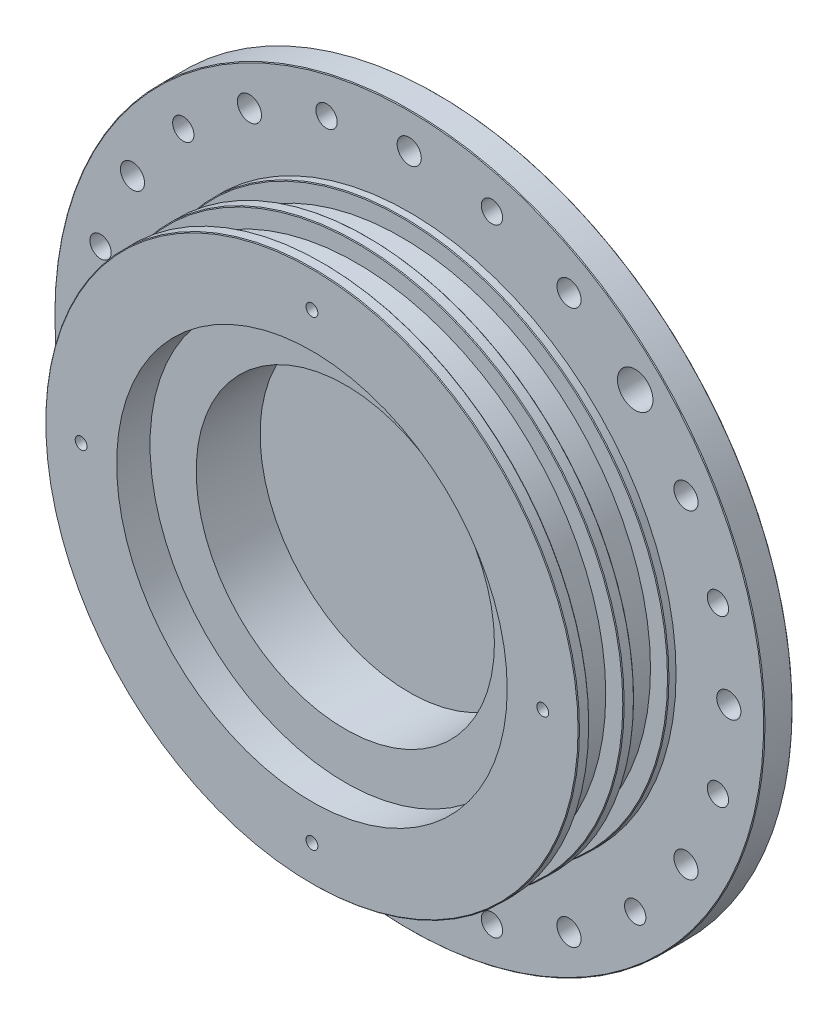
SolidWorks part; units mm, degrees
other "Marquage1"
sketch "Esquisse22" plane through (-100, 100, -114.225) normal (-0.6969, 0.6451, 0.3132) x (0.5706, 0.7634, -0.3027)
sketch "Esquisse26" plane through (-110, 110, -114.225) normal (-0.6969, 0.6451, 0.3132) x (0.5706, 0.7634, -0.3027)
sketch "Esquisse28" plane through (-110, 110, -114.225) normal (-0.6969, 0.6451, 0.3132) x (0.5706, 0.7634, -0.3027)
sketch "Esquisse31" plane through (-110, 110, -114.225) normal (-0.6969, 0.6451, 0.3132) x (0.5706, 0.7634, -0.3027)
sketch "Esquisse32" plane through (-100, 100, -114.225) normal (-0.6969, 0.6451, 0.3132) x (0.5706, 0.7634, -0.3027)
material "AISI 316 Barre d'acier inoxydable recuit (SS)"
ref_plane "Plan de face" through (0, 0, 0) normal (0, 0, 1) x (1, 0, 0)
ref_plane "Plan de dessus" through (0, 0, 0) normal (0, 1, 0) x (1, 0, 0)
ref_plane "Plan de droite" through (0, 0, 0) normal (1, 0, 0) x (0, 0, -1)
sketch "Esquisse1" plane through (0, 0, 0) normal (0, 1, 0) x (1, 0, 0)
  line L0 (87.5, 35.4) -> (0, 35.4)
  line L1 (0, 35.4) -> (0, 0)
  line L2 (0, 0) -> (75.15, 0)
  line L3 (75.15, 0) -> (75.15, 3)
  line L4 (75.15, 3) -> (70.15, 3)
  line L5 (70.15, 3) -> (70.15, 12.6)
  line L6 (70.15, 12.6) -> (75.15, 12.6)
  line L7 (75.15, 12.6) -> (75.15, 15.6)
  line L8 (75.15, 15.6) -> (70.15, 15.6)
  line L9 (70.15, 15.6) -> (70.15, 25.2)
  line L10 (70.15, 25.2) -> (75.15, 25.2)
  line L11 (75.15, 25.2) -> (75.15, 27.4)
  line L12 (75.15, 27.4) -> (87.5, 27.4)
  line L13 (87.5, 27.4) -> (87.5, 35.4)
  line L14 (0, 35.4) -> (0, 0) construction
  dimension "D1" = 8
  dimension "D2" = 2.2
  dimension "D3" = 9.6
  dimension "D4" = 3
  dimension "D5" = 9.6
  dimension "D6" = 3
  dimension "D7" = 5
  dimension "D8" = 75.15
  dimension "D9" = 87.5
revolve "Révolution1" add sketch "Esquisse1" angle 360 about L14 reverse direction yes
hole_wizard "Diamètre du perçage Ø9.0 (9)1" positions "Esquisse3" profile "Esquisse2" hole size "Ø9.0" standard "Ansi Metric"
sketch "Esquisse3" plane through (0, 0, -27.4) normal (0, 0, 1) x (1, 0, 0)
  point P0 (-87.5, 0)
  point P1 (0, 87.5)
  point P2 (0, -87.5)
  point P3 (87.5, 0)
sketch "Esquisse2" plane through (-87.5, 0, -27.4) normal (1, 0, 0) x (0, -1, 0)
  line L0 (0, 0) -> (0, 3)
  line L1 (0, 3) -> (4.5, 3)
  line L2 (4.5, 3) -> (4.5, 0)
  line L5 (4.5, 0) -> (0, 0)
  line L10 (0, 3) -> (-4.5, 3) construction
  line L11 (0, -6.35) -> (0, 107.95) construction
  dimension "Diamètre du perçage" = 9
  dimension "Profondeur du perçage" = 3
  dimension "Angle de pointe" = 180
hole_wizard "Dégagement M31" positions "Esquisse5" profile "Esquisse4" hole size "M3" standard "Ansi Metric"
sketch "Esquisse5" plane through (0, 0, 0) normal (0, 0, 1) x (1, 0, 0)
  point P0 (-65, 0)
  point P1 (65, 0)
  point P2 (0, 65)
  point P3 (0, -65)
sketch "Esquisse4" plane through (-65, 0, 0) normal (1, 0, 0) x (0, -1, 0)
  line L0 (0, 0) -> (0, 17.001)
  line L1 (0, 17.001) -> (1.666, 16)
  line L2 (1.666, 16) -> (1.666, 0)
  line L5 (1.666, 0) -> (0, 0)
  line L10 (0, 17.001) -> (-1.666, 16) construction
  line L11 (0, -6.35) -> (0, 107.95) construction
  dimension "Diamètre du perçage" = 3.332
  dimension "Profondeur du perçage" = 16
  dimension "Angle de pointe" = 118
hole_wizard "Dégagement M1001" positions "Esquisse7" profile "Esquisse6" hole size "M100" standard "Ansi Metric"
sketch "Esquisse7" plane through (0, 0, 0) normal (0, 0, 1) x (1, 0, 0)
  point P0 (0, 0)
sketch "Esquisse6" plane through (0, 0, 0) normal (1, 0, 0) x (0, -1, 0)
  line L0 (0, 0) -> (0, 27.4)
  line L1 (0, 27.4) -> (55, 27.4)
  line L2 (55, 27.4) -> (55, 0)
  line L5 (55, 0) -> (0, 0)
  line L10 (0, 27.4) -> (-55, 27.4) construction
  line L11 (0, -6.35) -> (0, 107.95) construction
  dimension "Diamètre du perçage" = 110
  dimension "Profondeur du perçage" = 27.4
  dimension "Angle de pointe" = 180
sketch "Esquisse8" plane through (0, 0, -35.4) normal (0, 0, -1) x (-1, 0, 0)
  line L0 (0, 0) -> (0, -108.9201) construction
  circle A0 centre (0, 0) radius 108.9201 construction
  circle A1 centre (0, 0) radius 100
  circle A2 centre (0, 0) radius 77.5
  circle A3 centre (0, 0) radius 87.5 construction
  dimension "D2" = 10
  dimension "D1" = 200
extrude "Boss.-Extru.1" add sketch "Esquisse8" against normal blind 8
ref_plane "Plan1" through (0, -100, 0) normal (0, -1, 0) x (-1, 0, 0)
sketch "Esquisse9" plane through (0, 0, -35.4) normal (0, 0, 1) x (1, 0, 0)
  line L0 (0, -50) -> (0, 0) construction
  circle A0 centre (0, -50) radius 3.4
  circle A17 centre (0, -90) radius 3.4
  circle A18 centre (-25, -43.3013) radius 3.4
  circle A19 centre (-45, -77.9423) radius 3.4
  circle A20 centre (-43.3013, -25) radius 3.4
  circle A21 centre (-77.9423, -45) radius 3.4
  circle A22 centre (-50, 0) radius 3.4
  circle A23 centre (-90, 0) radius 3.4
  circle A24 centre (-43.3013, 25) radius 3.4
  circle A25 centre (-77.9423, 45) radius 3.4
  circle A26 centre (-25, 43.3013) radius 3.4
  circle A27 centre (-45, 77.9423) radius 3.4
  circle A28 centre (0, 50) radius 3.4
  circle A29 centre (0, 90) radius 3.4
  circle A30 centre (25, 43.3013) radius 3.4
  circle A31 centre (45, 77.9423) radius 3.4
  circle A32 centre (43.3013, 25) radius 3.4
  circle A33 centre (77.9423, 45) radius 3.4
  circle A34 centre (50, 0) radius 3.4
  circle A35 centre (90, 0) radius 3.4
  circle A36 centre (43.3013, -25) radius 3.4
  circle A37 centre (77.9423, -45) radius 3.4
  circle A38 centre (25, -43.3013) radius 3.4
  circle A39 centre (45, -77.9423) radius 3.4
  point P17 (0, 0)
  point P28 (0, 0)
  point P31 (0, 0)
  point P55 (0, 0)
  dimension "D1" = 6.8
  dimension "D3" = 90
  dimension "D2" = 50
extrude "Enlèv. mat.-Extru.1" cut sketch "Esquisse9" along normal blind 20
sketch "Esquisse24" plane through (0, 0, -35.4) normal (0, 0, -1) x (-1, 0, 0)
  line L0 (28.0621, 104.7291) -> (0, 0) construction
  line L1 (-54.2118, 93.8976) -> (0, 0) construction
  line L2 (0, 0) -> (0, 90) construction
  line L3 (0, 0) -> (-63.6396, 63.6396) construction
  circle A0 centre (-45, 77.9423) radius 5 construction
  circle A1 centre (23.2937, 86.9333) radius 3
  circle A2 centre (63.6396, 63.6396) radius 3
  circle A3 centre (86.9333, 23.2937) radius 3
  circle A4 centre (86.9333, -23.2937) radius 3
  circle A5 centre (-14, 24.2487) radius 5
  circle A6 centre (7.2469, 27.0459) radius 5
  circle A7 centre (24.2487, 14) radius 5
  circle A8 centre (27.0459, -7.2469) radius 5
  circle A9 centre (14, -24.2487) radius 5
  circle A10 centre (-7.2469, -27.0459) radius 5
  circle A11 centre (-24.2487, -14) radius 5
  circle A12 centre (-27.0459, 7.2469) radius 5
  circle A13 centre (-63.6396, 63.6396) radius 5
  circle A14 centre (63.6396, -63.6396) radius 3
  circle A15 centre (23.2937, -86.9333) radius 3
  circle A16 centre (-23.2937, -86.9333) radius 3
  circle A17 centre (-63.6396, -63.6396) radius 3
  circle A18 centre (-86.9333, -23.2937) radius 3
  circle A19 centre (-86.9333, 23.2937) radius 3
  circle A20 centre (-63.6396, 63.6396) radius 3 construction
  circle A21 centre (-23.2937, 86.9333) radius 3
  circle A22 centre (0, 0) radius 82.55 construction
  circle A23 centre (-63.6396, 63.6396) radius 8 construction
  point P19 (0, 0)
  point P36 (0, 0)
  dimension "D1" = 6
  dimension "D3" = 10
  dimension "D6" = 10
  dimension "D11" = 15
  dimension "D12" = 10
  dimension "D14" = 165.1
  dimension "D15" = 16
  dimension "D2" = 90
  dimension "D4" = 90
  dimension "D7" = 28
  dimension "D9" = 45
  dimension "D10" = 15
  dimension "D13" = 90
  dimension "D5" = 12
  dimension "D8" = 8
extrude "Enlèv. mat.-Extru.15" cut sketch "Esquisse24" against normal through all and the other way through all
chamfer "Chanfrein1" distance 0.2 angle 45 7 edges at (75.15, 0, -25.2) (75.15, 0, -3) (75.15, 0, -12.6) (75.15, 0, -15.6) (-100, 0, -35.4) (-100, 0, -27.4) (75.15, 0, 0)
sketch "Esquisse25" plane through (0, 0, -35.4) normal (0, 0, -1) x (-1, 0, 0)
  line L0 (-24.9287, -1.7061) -> (-33.3561, 0.552) construction
  line L1 (-33.3561, 0.552) -> (-29.1632, 16.2) construction
  line L2 (-29.1632, 16.2) -> (-20.7358, 13.9419) construction
  line L3 (-20.7358, 13.9419) -> (-24.9287, -1.7061) construction
  line L4 (0, 0) -> (-31.2596, 8.376) construction
  line L5 (-27.0459, 7.2469) -> (-33.914, -18.3852) construction
  line L6 (-22.5347, 14.4239) -> (-27.3643, 15.718)
  line L7 (-26.7275, -1.2241) -> (-31.5572, 0.07)
  line L8 (-5.7352, 26.1336) -> (-8.2352, 30.4638)
  line L9 (-19.7648, 18.0336) -> (-22.2648, 22.3638)
  line L10 (14.4239, 22.5347) -> (15.718, 27.3643)
  line L11 (-1.2241, 26.7275) -> (0.07, 31.5572)
  line L12 (26.1336, 5.7352) -> (30.4638, 8.2352)
  line L13 (18.0336, 19.7648) -> (22.3638, 22.2648)
  line L14 (22.5347, -14.4239) -> (27.3643, -15.718)
  line L15 (26.7275, 1.2241) -> (31.5572, -0.07)
  line L16 (5.7352, -26.1336) -> (8.2352, -30.4638)
  line L17 (19.7648, -18.0336) -> (22.2648, -22.3638)
  line L18 (-14.4239, -22.5347) -> (-15.718, -27.3643)
  line L19 (1.2241, -26.7275) -> (-0.07, -31.5572)
  line L20 (-26.1336, -5.7352) -> (-30.4638, -8.2352)
  line L21 (-18.0336, -19.7648) -> (-22.3638, -22.2648)
  arc A2 (-33.3561, 0.552) -> (-29.1632, 16.2) centre (-27.0459, 7.2469) cw construction
  arc A3 (-24.9287, -1.7061) -> (-20.7358, 13.9419) centre (-27.0459, 7.2469) ccw construction
  arc A4 (-22.8033, -0.9164) -> (-19.29, 12.1953) centre (-27.0459, 7.2469) ccw
  arc A5 (-19.29, 12.1953) -> (-19.4952, 12.5745) centre (-16.7609, 13.8089) cw
  arc A6 (-19.4952, 12.5745) -> (-21.9939, 14.3309) centre (-22.2295, 11.3402) ccw
  arc A7 (-21.9939, 14.3309) -> (-22.5347, 14.4239) centre (-21.7582, 17.3217) cw
  arc A8 (-27.8791, 15.9079) -> (-27.3643, 15.718) centre (-26.5878, 18.6158) ccw
  arc A9 (-30.9212, 15.6361) -> (-27.8791, 15.9079) centre (-29.1704, 13.2) cw
  arc A10 (-31.2885, 15.4103) -> (-30.9212, 15.6361) centre (-32.672, 18.0722) ccw
  arc A11 (-34.8018, 2.2986) -> (-31.2885, 15.4103) centre (-27.0459, 7.2469) cw
  arc A12 (-34.8018, 2.2986) -> (-34.5966, 1.9193) centre (-37.3309, 0.685) cw
  arc A13 (-34.5966, 1.9193) -> (-32.098, 0.1629) centre (-31.8623, 3.1537) ccw
  arc A14 (-32.098, 0.1629) -> (-31.5572, 0.07) centre (-32.3336, -2.8278) cw
  arc A15 (-26.2127, -1.414) -> (-26.7275, -1.2241) centre (-27.504, -4.1219) ccw
  arc A16 (-23.1707, -1.1423) -> (-26.2127, -1.414) centre (-24.9215, 1.2939) cw
  arc A17 (-22.8033, -0.9164) -> (-23.1707, -1.1423) centre (-21.4198, -3.5784) ccw
  arc A19 (-22.9833, 26.2339) -> (-11.2276, 33.0211) centre (-14, 24.2487) cw
  arc A20 (-11.2276, 33.0211) -> (-10.8082, 32.921) centre (-10.3236, 35.8816) ccw
  arc A21 (-10.8082, 32.921) -> (-8.4649, 30.9621) centre (-11.2928, 29.9604) cw
  arc A22 (-8.4649, 30.9621) -> (-8.2352, 30.4638) centre (-5.6371, 31.9638) ccw
  arc A23 (-5.4185, 25.6855) -> (-5.7352, 26.1336) centre (-3.1371, 27.6336) cw
  arc A24 (-4.8937, 22.6768) -> (-5.4185, 25.6855) centre (-7.6999, 23.7374) ccw
  arc A25 (-5.0167, 22.2635) -> (-4.8937, 22.6768) centre (-2.0874, 21.6161) cw
  arc A26 (-16.7724, 15.4764) -> (-5.0167, 22.2635) centre (-14, 24.2487) ccw
  arc A27 (-16.7724, 15.4764) -> (-17.1918, 15.5764) centre (-17.6764, 12.6158) ccw
  arc A28 (-17.1918, 15.5764) -> (-19.5351, 17.5353) centre (-16.7072, 18.537) cw
  arc A29 (-19.5351, 17.5353) -> (-19.7648, 18.0336) centre (-22.3629, 16.5336) ccw
  arc A30 (-22.5815, 22.8119) -> (-22.2648, 22.3638) centre (-24.8629, 20.8638) cw
  arc A31 (-23.1063, 25.8207) -> (-22.5815, 22.8119) centre (-20.3001, 24.76) ccw
  arc A32 (-22.9833, 26.2339) -> (-23.1063, 25.8207) centre (-25.9126, 26.8813) cw
  arc A33 (2.2986, 34.8018) -> (15.4103, 31.2885) centre (7.2469, 27.0459) cw
  arc A34 (15.4103, 31.2885) -> (15.6361, 30.9212) centre (18.0722, 32.672) ccw
  arc A35 (15.6361, 30.9212) -> (15.9079, 27.8791) centre (13.2, 29.1704) cw
  arc A36 (15.9079, 27.8791) -> (15.718, 27.3643) centre (18.6158, 26.5878) ccw
  arc A37 (14.3309, 21.9939) -> (14.4239, 22.5347) centre (17.3217, 21.7582) cw
  arc A38 (12.5745, 19.4952) -> (14.3309, 21.9939) centre (11.3402, 22.2295) ccw
  arc A39 (12.1953, 19.29) -> (12.5745, 19.4952) centre (13.8089, 16.7609) cw
  arc A40 (-0.9164, 22.8033) -> (12.1953, 19.29) centre (7.2469, 27.0459) ccw
  arc A41 (-0.9164, 22.8033) -> (-1.1423, 23.1707) centre (-3.5784, 21.4198) ccw
  arc A42 (-1.1423, 23.1707) -> (-1.414, 26.2127) centre (1.2939, 24.9215) cw
  arc A43 (-1.414, 26.2127) -> (-1.2241, 26.7275) centre (-4.1219, 27.504) ccw
  arc A44 (0.1629, 32.098) -> (0.07, 31.5572) centre (-2.8278, 32.3336) cw
  arc A45 (1.9193, 34.5966) -> (0.1629, 32.098) centre (3.1537, 31.8623) ccw
  arc A46 (2.2986, 34.8018) -> (1.9193, 34.5966) centre (0.685, 37.3309) cw
  arc A47 (26.2339, 22.9833) -> (33.0211, 11.2276) centre (24.2487, 14) cw
  arc A48 (33.0211, 11.2276) -> (32.921, 10.8082) centre (35.8816, 10.3236) ccw
  arc A49 (32.921, 10.8082) -> (30.9621, 8.4649) centre (29.9604, 11.2928) cw
  arc A50 (30.9621, 8.4649) -> (30.4638, 8.2352) centre (31.9638, 5.6371) ccw
  arc A51 (25.6855, 5.4185) -> (26.1336, 5.7352) centre (27.6336, 3.1371) cw
  arc A52 (22.6768, 4.8937) -> (25.6855, 5.4185) centre (23.7374, 7.6999) ccw
  arc A53 (22.2635, 5.0167) -> (22.6768, 4.8937) centre (21.6161, 2.0874) cw
  arc A54 (15.4764, 16.7724) -> (22.2635, 5.0167) centre (24.2487, 14) ccw
  arc A55 (15.4764, 16.7724) -> (15.5764, 17.1918) centre (12.6158, 17.6764) ccw
  arc A56 (15.5764, 17.1918) -> (17.5353, 19.5351) centre (18.537, 16.7072) cw
  arc A57 (17.5353, 19.5351) -> (18.0336, 19.7648) centre (16.5336, 22.3629) ccw
  arc A58 (22.8119, 22.5815) -> (22.3638, 22.2648) centre (20.8638, 24.8629) cw
  arc A59 (25.8207, 23.1063) -> (22.8119, 22.5815) centre (24.76, 20.3001) ccw
  arc A60 (26.2339, 22.9833) -> (25.8207, 23.1063) centre (26.8813, 25.9126) cw
  arc A61 (34.8018, -2.2986) -> (31.2885, -15.4103) centre (27.0459, -7.2469) cw
  arc A62 (31.2885, -15.4103) -> (30.9212, -15.6361) centre (32.672, -18.0722) ccw
  arc A63 (30.9212, -15.6361) -> (27.8791, -15.9079) centre (29.1704, -13.2) cw
  arc A64 (27.8791, -15.9079) -> (27.3643, -15.718) centre (26.5878, -18.6158) ccw
  arc A65 (21.9939, -14.3309) -> (22.5347, -14.4239) centre (21.7582, -17.3217) cw
  arc A66 (19.4952, -12.5745) -> (21.9939, -14.3309) centre (22.2295, -11.3402) ccw
  arc A67 (19.29, -12.1953) -> (19.4952, -12.5745) centre (16.7609, -13.8089) cw
  arc A68 (22.8033, 0.9164) -> (19.29, -12.1953) centre (27.0459, -7.2469) ccw
  arc A69 (22.8033, 0.9164) -> (23.1707, 1.1423) centre (21.4198, 3.5784) ccw
  arc A70 (23.1707, 1.1423) -> (26.2127, 1.414) centre (24.9215, -1.2939) cw
  arc A71 (26.2127, 1.414) -> (26.7275, 1.2241) centre (27.504, 4.1219) ccw
  arc A72 (32.098, -0.1629) -> (31.5572, -0.07) centre (32.3336, 2.8278) cw
  arc A73 (34.5966, -1.9193) -> (32.098, -0.1629) centre (31.8623, -3.1537) ccw
  arc A74 (34.8018, -2.2986) -> (34.5966, -1.9193) centre (37.3309, -0.685) cw
  arc A75 (22.9833, -26.2339) -> (11.2276, -33.0211) centre (14, -24.2487) cw
  arc A76 (11.2276, -33.0211) -> (10.8082, -32.921) centre (10.3236, -35.8816) ccw
  arc A77 (10.8082, -32.921) -> (8.4649, -30.9621) centre (11.2928, -29.9604) cw
  arc A78 (8.4649, -30.9621) -> (8.2352, -30.4638) centre (5.6371, -31.9638) ccw
  arc A79 (5.4185, -25.6855) -> (5.7352, -26.1336) centre (3.1371, -27.6336) cw
  arc A80 (4.8937, -22.6768) -> (5.4185, -25.6855) centre (7.6999, -23.7374) ccw
  arc A81 (5.0167, -22.2635) -> (4.8937, -22.6768) centre (2.0874, -21.6161) cw
  arc A82 (16.7724, -15.4764) -> (5.0167, -22.2635) centre (14, -24.2487) ccw
  arc A83 (16.7724, -15.4764) -> (17.1918, -15.5764) centre (17.6764, -12.6158) ccw
  arc A84 (17.1918, -15.5764) -> (19.5351, -17.5353) centre (16.7072, -18.537) cw
  arc A85 (19.5351, -17.5353) -> (19.7648, -18.0336) centre (22.3629, -16.5336) ccw
  arc A86 (22.5815, -22.8119) -> (22.2648, -22.3638) centre (24.8629, -20.8638) cw
  arc A87 (23.1063, -25.8207) -> (22.5815, -22.8119) centre (20.3001, -24.76) ccw
  arc A88 (22.9833, -26.2339) -> (23.1063, -25.8207) centre (25.9126, -26.8813) cw
  arc A89 (-2.2986, -34.8018) -> (-15.4103, -31.2885) centre (-7.2469, -27.0459) cw
  arc A90 (-15.4103, -31.2885) -> (-15.6361, -30.9212) centre (-18.0722, -32.672) ccw
  arc A91 (-15.6361, -30.9212) -> (-15.9079, -27.8791) centre (-13.2, -29.1704) cw
  arc A92 (-15.9079, -27.8791) -> (-15.718, -27.3643) centre (-18.6158, -26.5878) ccw
  arc A93 (-14.3309, -21.9939) -> (-14.4239, -22.5347) centre (-17.3217, -21.7582) cw
  arc A94 (-12.5745, -19.4952) -> (-14.3309, -21.9939) centre (-11.3402, -22.2295) ccw
  arc A95 (-12.1953, -19.29) -> (-12.5745, -19.4952) centre (-13.8089, -16.7609) cw
  arc A96 (0.9164, -22.8033) -> (-12.1953, -19.29) centre (-7.2469, -27.0459) ccw
  arc A97 (0.9164, -22.8033) -> (1.1423, -23.1707) centre (3.5784, -21.4198) ccw
  arc A98 (1.1423, -23.1707) -> (1.414, -26.2127) centre (-1.2939, -24.9215) cw
  arc A99 (1.414, -26.2127) -> (1.2241, -26.7275) centre (4.1219, -27.504) ccw
  arc A100 (-0.1629, -32.098) -> (-0.07, -31.5572) centre (2.8278, -32.3336) cw
  arc A101 (-1.9193, -34.5966) -> (-0.1629, -32.098) centre (-3.1537, -31.8623) ccw
  arc A102 (-2.2986, -34.8018) -> (-1.9193, -34.5966) centre (-0.685, -37.3309) cw
  arc A103 (-26.2339, -22.9833) -> (-33.0211, -11.2276) centre (-24.2487, -14) cw
  arc A104 (-33.0211, -11.2276) -> (-32.921, -10.8082) centre (-35.8816, -10.3236) ccw
  arc A105 (-32.921, -10.8082) -> (-30.9621, -8.4649) centre (-29.9604, -11.2928) cw
  arc A106 (-30.9621, -8.4649) -> (-30.4638, -8.2352) centre (-31.9638, -5.6371) ccw
  arc A107 (-25.6855, -5.4185) -> (-26.1336, -5.7352) centre (-27.6336, -3.1371) cw
  arc A108 (-22.6768, -4.8937) -> (-25.6855, -5.4185) centre (-23.7374, -7.6999) ccw
  arc A109 (-22.2635, -5.0167) -> (-22.6768, -4.8937) centre (-21.6161, -2.0874) cw
  arc A110 (-15.4764, -16.7724) -> (-22.2635, -5.0167) centre (-24.2487, -14) ccw
  arc A111 (-15.4764, -16.7724) -> (-15.5764, -17.1918) centre (-12.6158, -17.6764) ccw
  arc A112 (-15.5764, -17.1918) -> (-17.5353, -19.5351) centre (-18.537, -16.7072) cw
  arc A113 (-17.5353, -19.5351) -> (-18.0336, -19.7648) centre (-16.5336, -22.3629) ccw
  arc A114 (-22.8119, -22.5815) -> (-22.3638, -22.2648) centre (-20.8638, -24.8629) cw
  arc A115 (-25.8207, -23.1063) -> (-22.8119, -22.5815) centre (-24.76, -20.3001) ccw
  arc A116 (-26.2339, -22.9833) -> (-25.8207, -23.1063) centre (-26.8813, -25.9126) cw
  point P7 (-22.8322, 6.1179)
  point P35 (-24.9495, 15.0709)
  point P250 (0, 0)
  dimension "D1" = 9.2
  dimension "D3" = 3
  dimension "D4" = 2.5
  dimension "D2" = 16.2
  dimension "D5" = 8
extrude "Enlèv. mat.-Extru.18" cut sketch "Esquisse25" against normal blind 2
sketch "Esquisse35" plane through (0, 0, -27.4) normal (0, 0, 1) x (1, 0, 0)
  circle A0 centre (0, 0) radius 55
  circle A1 centre (0, 0) radius 42
  circle A4 centre (0, 0) radius 55 construction
  dimension "D1" = 84
extrude "Boss.-Extru.4" add sketch "Esquisse35" along normal blind 18
sketch "Esquisse36" plane through (0, 0, -27.4) normal (0, 0, 1) x (1, 0, 0)
  circle A0 centre (-27.0459, -7.2469) radius 5
  circle A1 centre (-27.0459, -7.2469) radius 5 construction
  circle A2 centre (-24.2487, 14) radius 5
  circle A3 centre (-7.2469, 27.0459) radius 5
  circle A4 centre (14, 24.2487) radius 5
  circle A5 centre (27.0459, 7.2469) radius 5
  circle A6 centre (24.2487, -14) radius 5
  circle A7 centre (7.2469, -27.0459) radius 5
  circle A8 centre (-14, -24.2487) radius 5
  point P14 (0, 0)
  dimension "D1" = 8
extrude "Boss.-Extru.5" add sketch "Esquisse36" against normal blind 4
extrude "Enlèv. mat.-Extru.20" cut sketch "Esquisse9<2>" along normal blind 20
sketch "Esquisse9<2>" plane through (0, 0, -35.4) normal (0, 0, 1) x (1, 0, 0) same geometry as "Esquisse9"
equation "\"_à\"=76.5769"
